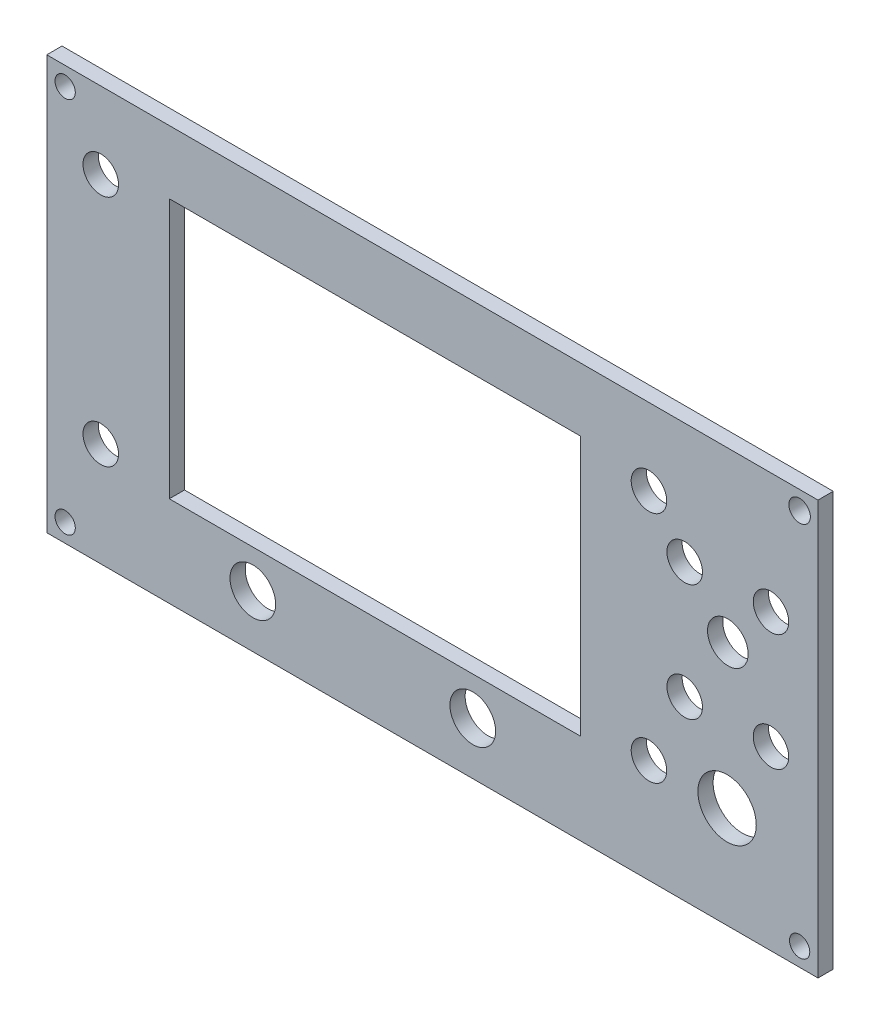
SolidWorks part; units mm, degrees
ref_plane "Plan de face" through (0, 0, 0) normal (0, 0, 1) x (1, 0, 0)
ref_plane "Plan de dessus" through (0, 0, 0) normal (0, 1, 0) x (1, 0, 0)
ref_plane "Plan de droite" through (0, 0, 0) normal (1, 0, 0) x (0, 0, -1)
sketch "Esquisse1" plane through (0, 0, 0.8) normal (0, 0, 1) x (1, 0, 0)
  line L0 (-95.6944, -23.7786) -> (-9.1944, -23.7786) construction
  line L1 (-112.5896, 39.9055) -> (24.8649, 39.9055)
  line L2 (-119.8323, 32.6629) -> (-119.8323, -34.3961)
  line L3 (-112.5896, -41.6387) -> (24.8649, -41.6387)
  line L4 (32.1075, 32.6629) -> (32.1075, -34.3961)
  line L5 (-95.6944, 27.4214) -> (-14.6944, 27.4214)
  line L6 (-95.6944, 27.4214) -> (-95.6944, -23.7786)
  line L7 (-95.6944, -23.7786) -> (-14.6944, -23.7786)
  line L8 (-14.6944, 27.4214) -> (-14.6944, -23.7786)
  line L9 (-15.1944, -23.2786) -> (-15.1944, 26.9214) construction
  line L11 (-112.5896, 35.6629) -> (-112.5896, 39.9055)
  line L12 (-115.5896, 32.6629) -> (-119.8323, 32.6629)
  line L13 (-43.8624, -38.6114) -> (-43.8624, 39.9055) construction
  line L14 (32.1075, -0.8666) -> (-119.8323, -0.8666) construction
  line L15 (24.8649, 35.6629) -> (24.8649, 39.9055)
  line L16 (27.8649, 32.6629) -> (32.1075, 32.6629)
  line L17 (-112.5896, -37.3961) -> (-112.5896, -41.6387)
  line L18 (-115.5896, -34.3961) -> (-119.8323, -34.3961)
  line L19 (24.8649, -37.3961) -> (24.8649, -41.6387)
  line L20 (27.8649, -34.3961) -> (32.1075, -34.3961)
  line L21 (32.1075, -41.6387) -> (32.1075, 39.9055) construction
  line L22 (-119.8323, -41.6387) -> (32.1075, -41.6387) construction
  line L24 (-119.8323, 39.9055) -> (-119.8323, -41.6387) construction
  line L25 (-112.5896, -41.6387) -> (-119.8323, -34.3961) construction
  line L26 (32.1075, 39.9055) -> (-119.8323, 39.9055) construction
  line L27 (-112.5896, 39.9055) -> (-119.8323, 32.6629) construction
  line L28 (-112.5896, -37.3961) -> (-112.5896, -41.6387) construction
  circle A0 centre (-109.1944, 24.8214) radius 3.5
  circle A1 centre (-1.1944, 24.8214) radius 3.5
  circle A2 centre (-1.1944, -21.1786) radius 3.5
  circle A3 centre (-109.1944, -21.1786) radius 3.5
  arc A4 (-115.5896, 32.6629) -> (-112.5896, 35.6629) centre (-115.5896, 35.6629) ccw
  arc A5 (27.8649, 32.6629) -> (24.8649, 35.6629) centre (27.8649, 35.6629) cw
  arc A6 (-115.5896, -34.3961) -> (-112.5896, -37.3961) centre (-115.5896, -37.3961) cw
  arc A7 (27.8649, -34.3961) -> (24.8649, -37.3961) centre (27.8649, -37.3961) ccw
  circle A8 centre (14.3452, 6.7499) radius 4
  circle A9 centre (5.8452, 16.2043) radius 3.5
  circle A10 centre (22.8452, 16.2043) radius 3.5
  circle A11 centre (22.8452, -6.7957) radius 3.5
  circle A12 centre (5.8452, -6.7957) radius 3.5
  circle A13 centre (14.1946, -21.6387) radius 5.75
  circle A15 centre (-35.9056, -31.3167) radius 4.5
  circle A16 centre (-79.2375, -31.3167) radius 4.5
  circle A17 centre (-109.1944, 24.8214) radius 2 construction
  circle A18 centre (-109.1944, -21.1786) radius 2 construction
  circle A19 centre (-1.1944, -21.1786) radius 2 construction
  circle A20 centre (-1.1944, 24.8214) radius 2 construction
  circle A21 centre (14.1946, -21.6387) radius 3.25 construction
  point P72 (32.1075, -0.8666)
  dimension "D1" = 7
  dimension "D4" = 3
  dimension "D6" = 11.5
  dimension "D7" = 9
  dimension "D8" = 9
  dimension "D2" = 0.5
  dimension "D3" = 45
  dimension "D5" = 45
extrude "Boss.-Extru.1" add sketch "Esquisse1" along normal blind 3
sketch "Esquisse2" plane through (0, 0, 0.8) normal (0, 0, 1) x (1, 0, 0)
  line L1 (-112.5896, -41.6387) -> (-119.8323, -41.6387)
  line L2 (-112.5896, -41.6387) -> (-112.5896, -34.3961)
  line L3 (-112.5896, -34.3961) -> (-119.8323, -34.3961)
  line L4 (-119.8323, -41.6387) -> (-119.8323, -34.3961)
  line L5 (-112.5896, 39.9055) -> (-119.8323, 39.9055)
  line L6 (-112.5896, 39.9055) -> (-112.5896, 32.6629)
  line L7 (-112.5896, 32.6629) -> (-119.8323, 32.6629)
  line L8 (-119.8323, 39.9055) -> (-119.8323, 32.6629)
  line L9 (24.8649, 39.9055) -> (32.1075, 39.9055)
  line L10 (24.8649, 39.9055) -> (24.8649, 32.6629)
  line L11 (24.8649, 32.6629) -> (32.1075, 32.6629)
  line L12 (32.1075, 39.9055) -> (32.1075, 32.6629)
  line L13 (32.1075, -34.3961) -> (24.8649, -34.3961)
  line L14 (32.1075, -34.3961) -> (32.1075, -41.6387)
  line L15 (32.1075, -41.6387) -> (24.8649, -41.6387)
  line L16 (24.8649, -34.3961) -> (24.8649, -41.6387)
  circle A0 centre (-116.211, -38.0174) radius 1.9653
  circle A1 centre (28.4862, 36.2842) radius 2.1135
  circle A2 centre (-116.211, 36.2842) radius 2
  circle A3 centre (28.4862, -38.0174) radius 2
  circle M10 centre (-116.211, 36.2842) radius 2
  line M13 (-119.8323, 39.9055) -> (-119.8323, -41.6387)
  line M14 (-119.8323, -41.6387) -> (32.1075, -41.6387)
  line M15 (32.1075, -41.6387) -> (32.1075, 39.9055)
  line M16 (32.1075, 39.9055) -> (-119.8323, 39.9055)
  circle M27 centre (-116.211, -38.0174) radius 2
  circle M28 centre (28.4862, -38.0174) radius 2
extrude "Boss.-Extru.2" add sketch "Esquisse2" along normal blind 3 contours L7 L6 M16 M13 M10 | L10 L11 A1 M15 M16 | L13 L16 L15 M28 M15 | L2 L3 M13 M14 M27 region at (-116.211, -41.5363, 0.8) region at (24.9673, -38.0174, 0.8) region at (-119.7298, 36.2842, 0.8) region at (28.4862, 32.7653, 0.8)
